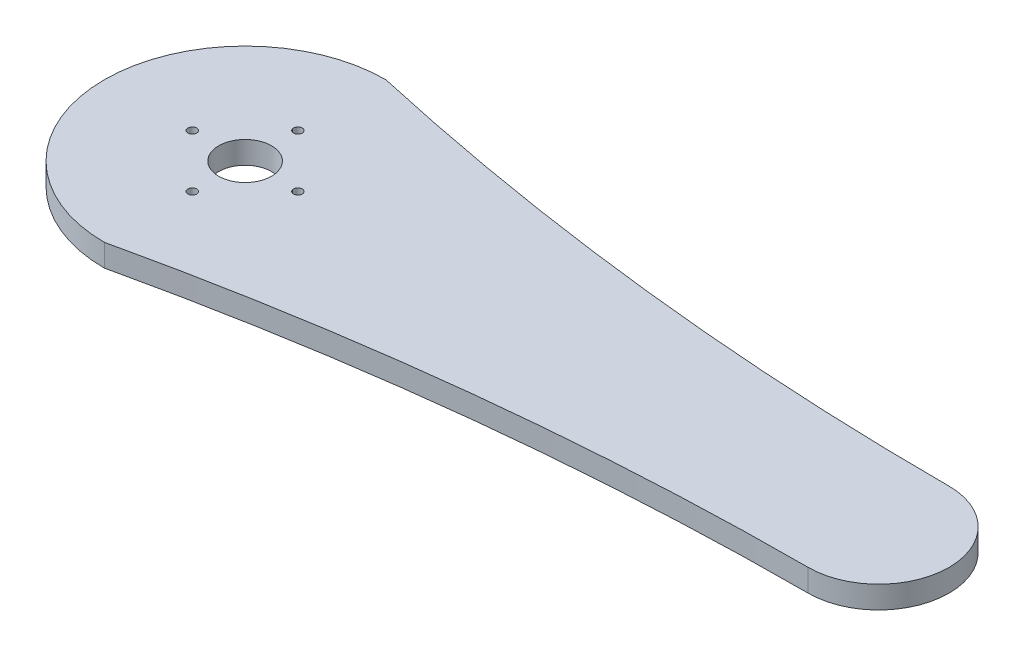
SolidWorks part; units mm, degrees
material "Pine"
ref_plane "Front Plane" through (0, 0, 0) normal (0, 0, 1) x (1, 0, 0)
ref_plane "Top Plane" through (0, 0, 0) normal (0, 1, 0) x (1, 0, 0)
ref_plane "Right Plane" through (0, 0, 0) normal (1, 0, 0) x (0, 0, -1)
sketch "Sketch3" plane through (0, 0, 0) normal (0, 1, 0) x (1, 0, 0)
  line L0 (-40.3723, 0) -> (-32.2473, 0) construction
  arc A0 (-40.3723, 20) -> (-40.3723, -20) centre (-40.3723, 0) ccw
  circle A2 centre (-40.3723, 0) radius 3.75
  circle A3 centre (-32.8723, 0) radius 0.625
  circle A8 centre (-47.8723, 0) radius 0.625
  circle A9 centre (-40.3723, 7.5) radius 0.625
  circle A10 centre (-40.3723, -7.5) radius 0.625
  arc A11 (49.6277, 10) -> (49.6277, -10) centre (49.6277, 0) cw
  arc A12 (49.6277, 10) -> (-40.3723, 20) centre (49.6277, 420) cw
  arc A13 (49.6277, -10) -> (-40.3723, -20) centre (49.6277, -420) ccw
  point P3 (-0.3723, 0)
  dimension "D1" = 20
  dimension "D7" = 7.5
  dimension "D9" = 1.25
  dimension "D3" = 10
  dimension "D2" = 90
  dimension "D10" = 7.5
  dimension "D12" = 7.5
  dimension "D13" = 7.5
  dimension "D16" = 7.5
extrude "Boss-Extrude1" add sketch "Sketch3" along normal blind 3.175
